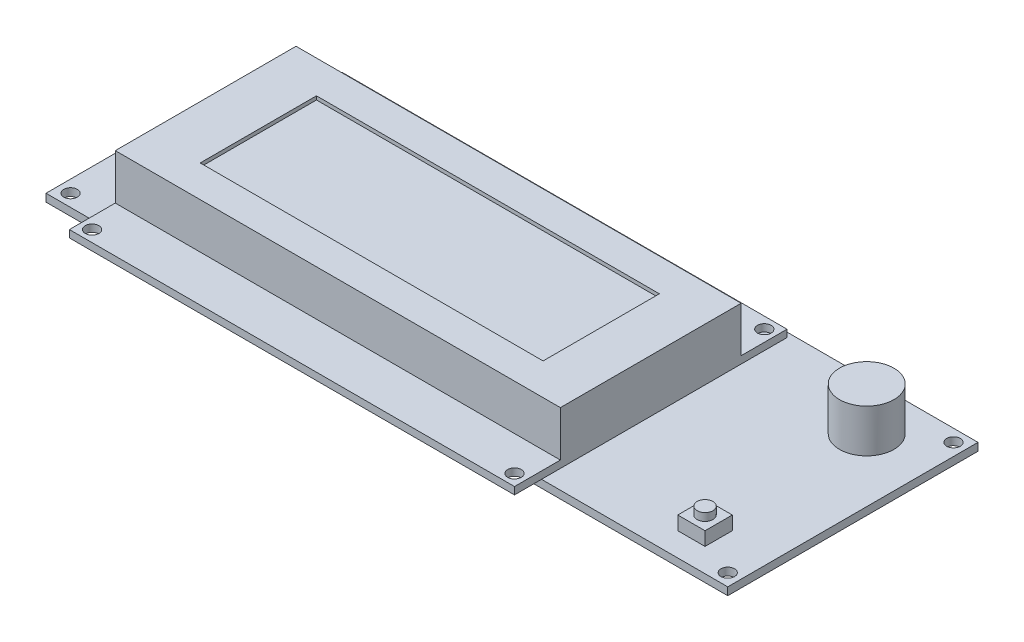
SolidWorks part; units mm, degrees
ref_plane "Front Plane" through (0, 0, 0) normal (0, 0, 1) x (1, 0, 0)
ref_plane "Top Plane" through (0, 0, 0) normal (0, 1, 0) x (1, 0, 0)
ref_plane "Right Plane" through (0, 0, 0) normal (1, 0, 0) x (0, 0, -1)
sketch "Sketch1" plane through (0, 0, 0) normal (0, 1, 0) x (1, 0, 0)
  line L1 (-75.05, -27.55) -> (75.05, -27.55)
  line L2 (-75.05, -27.55) -> (-75.05, 27.55)
  line L3 (-75.05, 27.55) -> (75.05, 27.55)
  line L4 (75.05, -27.55) -> (75.05, 27.55)
  line L5 (-75.05, -27.55) -> (75.05, 27.55) construction
  line L6 (-75.05, 27.55) -> (75.05, -27.55) construction
  circle A0 centre (-72.35, 24.85) radius 1.5
  circle A1 centre (-72.35, -24.85) radius 1.5
  circle A2 centre (72.35, 24.85) radius 1.5
  circle A3 centre (72.35, -24.85) radius 1.5
  point P0 (0, 0)
  dimension "D3" = 3
  dimension "D4" = 2.7
  dimension "D5" = 2.7
  dimension "D6" = 3
  dimension "D7" = 2.7
  dimension "D8" = 2.7
  dimension "D9" = 3
  dimension "D10" = 2.7
  dimension "D11" = 2.7
  dimension "D12" = 3
  dimension "D14" = 2.7
  dimension "D1" = 55.1
  dimension "D2" = 150.1
  dimension "D13" = 2.7
extrude "Boss-Extrude1" add sketch "Sketch1" along normal blind 1.7
sketch "Sketch2" plane through (0, 1.7, 0) normal (0, 1, 0) x (1, 0, 0)
  line L0 (-75.05, 27.55) -> (-75.05, -27.55) construction
  line L1 (-53.25, 23.15) -> (-12.45, 23.15)
  line L2 (-53.25, 23.15) -> (-53.25, 20.65)
  line L3 (-53.25, 20.65) -> (-12.45, 20.65)
  line L4 (-12.45, 23.15) -> (-12.45, 20.65)
  line L5 (75.05, 27.55) -> (-75.05, 27.55) construction
  dimension "D1" = 40.8
  dimension "D2" = 2.5
  dimension "D3" = 21.8
  dimension "D4" = 4.4
extrude "Boss-Extrude2" add sketch "Sketch2" along normal blind 2.4
sketch "Sketch3" plane through (0, 4.1, 0) normal (0, 1, 0) x (1, 0, 0)
  line L0 (75.05, 27.55) -> (-75.05, 27.55) construction
  line L1 (-61.55, 24.1) -> (36.45, 24.1)
  line L2 (-61.55, 24.1) -> (-61.55, -35.9)
  line L3 (-61.55, -35.9) -> (36.45, -35.9)
  line L4 (36.45, 24.1) -> (36.45, -35.9)
  line L5 (-75.05, 27.55) -> (-75.05, -27.55) construction
  circle A0 centre (-59.05, 21.6) radius 1.5
  circle A1 centre (33.95, 21.6) radius 1.5
  circle A2 centre (33.95, -33.4) radius 1.5
  circle A3 centre (-59.05, -33.4) radius 1.5
  point P16 (0, 0)
  point P17 (0, 0)
  dimension "D5" = 3
  dimension "D6" = 2.5
  dimension "D7" = 2.5
  dimension "D8" = 2.5
  dimension "D9" = 2.5
  dimension "D1" = 60
  dimension "D2" = 98
  dimension "D3" = 3.45
  dimension "D4" = 13.5
extrude "Boss-Extrude3" add sketch "Sketch3" along normal blind 1.6
sketch "Sketch4" plane through (0, 5.7, 0) normal (0, 1, 0) x (1, 0, 0)
  line L0 (-61.55, 24.1) -> (-61.55, -35.9) construction
  line L1 (-61.55, 14) -> (36.45, 14)
  line L2 (-61.55, 14) -> (-61.55, -25.8)
  line L3 (-61.55, -25.8) -> (36.45, -25.8)
  line L4 (36.45, 14) -> (36.45, -25.8)
  line L5 (36.45, -35.9) -> (36.45, 24.1) construction
  line L6 (-61.55, -35.9) -> (36.45, -35.9) construction
  dimension "D1" = 39.8
  dimension "D2" = 10.1
extrude "Boss-Extrude4" add sketch "Sketch4" along normal blind 10
sketch "Sketch5" plane through (0, 15.7, 0) normal (0, 1, 0) x (1, 0, 0)
  line L0 (-61.55, -25.8) -> (36.45, -25.8) construction
  line L1 (-49.85, 6.8) -> (25.65, 6.8)
  line L2 (-49.85, 6.8) -> (-49.85, -18.8)
  line L3 (-49.85, -18.8) -> (25.65, -18.8)
  line L4 (25.65, 6.8) -> (25.65, -18.8)
  line L5 (36.45, -25.8) -> (36.45, 14) construction
  dimension "D1" = 7
  dimension "D2" = 10.8
  dimension "D3" = 25.6
  dimension "D4" = 75.5
extrude "Cut-Extrude1" cut sketch "Sketch5" against normal blind 0.8
sketch "Sketch6" plane through (0, 1.7, 0) normal (0, 1, 0) x (1, 0, 0)
  line L0 (75.05, 27.55) -> (-75.05, 27.55) construction
  line L1 (75.05, -27.55) -> (75.05, 27.55) construction
  circle A0 centre (61.15, 16.95) radius 6
  dimension "D1" = 12
  dimension "D2" = 10.6
  dimension "D3" = 13.9
extrude "Boss-Extrude5" add sketch "Sketch6" along normal blind 9.5
sketch "Sketch7" plane through (0, 1.7, 0) normal (0, 1, 0) x (1, 0, 0)
  line L0 (-75.05, -27.55) -> (75.05, -27.55) construction
  line L1 (58.85, -16.35) -> (64.85, -16.35)
  line L2 (58.85, -16.35) -> (58.85, -22.35)
  line L3 (58.85, -22.35) -> (64.85, -22.35)
  line L4 (64.85, -16.35) -> (64.85, -22.35)
  line L5 (75.05, -27.55) -> (75.05, 27.55) construction
  dimension "D1" = 6
  dimension "D2" = 6
  dimension "D3" = 5.2
  dimension "D4" = 10.2
extrude "Boss-Extrude6" add sketch "Sketch7" along normal blind 3
sketch "Sketch8" plane through (0, 4.7, 0) normal (0, 1, 0) x (1, 0, 0)
  line L1 (64.85, -22.35) -> (64.85, -16.35) construction
  line L2 (58.85, -22.35) -> (64.85, -22.35) construction
  circle A0 centre (61.85, -19.35) radius 1.75
  point P2 (0, 0)
  point P5 (0, 0)
  point P8 (64.85, -19.35)
  point P9 (61.85, -22.35)
  dimension "D1" = 3.5
extrude "Boss-Extrude7" add sketch "Sketch8" along normal blind 1.7
